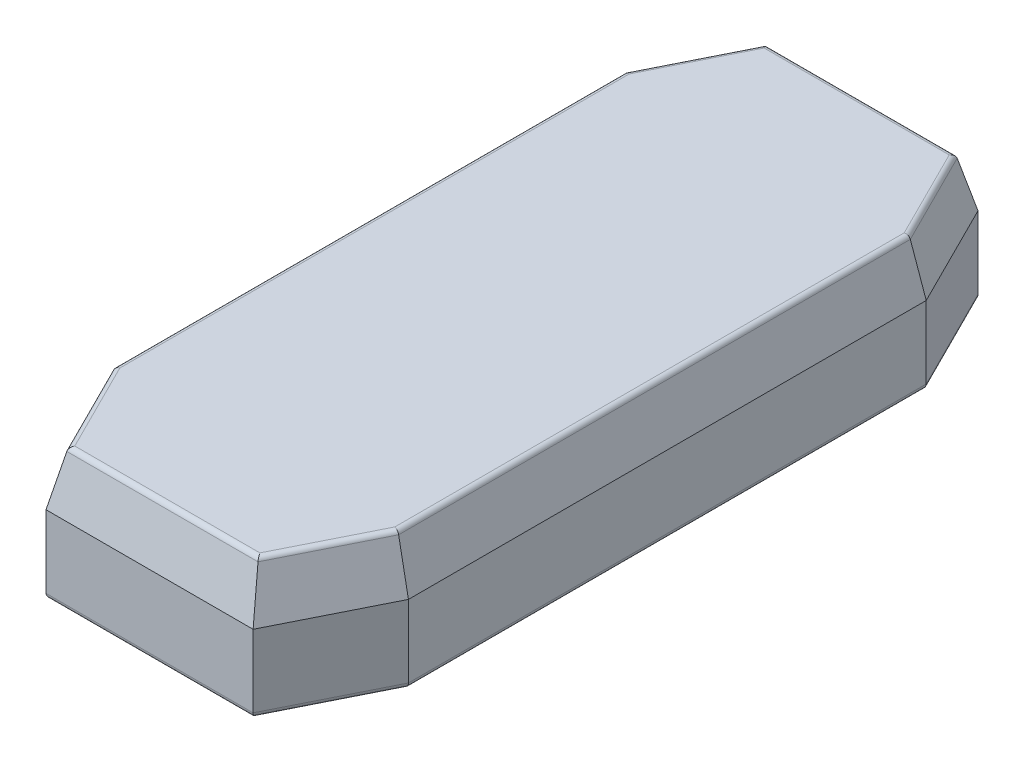
SolidWorks part; units mm, degrees
ref_plane "Front Plane" through (0, 0, 0) normal (0, 0, 1) x (1, 0, 0)
ref_plane "Top Plane" through (0, 0, 0) normal (0, 1, 0) x (1, 0, 0)
ref_plane "Right Plane" through (0, 0, 0) normal (1, 0, 0) x (0, 0, -1)
sketch "Sketch1" plane through (0, 0, 0) normal (0, 1, 0) x (1, 0, 0)
  line L0 (-7.62, 12.7) -> (-5.08, 17.78)
  line L1 (-5.08, 17.78) -> (5.08, 17.78)
  line L2 (-7.62, 12.7) -> (-7.62, -12.7)
  line L3 (-5.08, -17.78) -> (5.08, -17.78)
  line L4 (7.62, 12.7) -> (7.62, -12.7)
  line L5 (-7.62, 17.78) -> (7.62, -17.78) construction
  line L6 (-7.62, -17.78) -> (7.62, 17.78) construction
  line L7 (5.08, 17.78) -> (7.62, 12.7)
  line L8 (5.08, -17.78) -> (7.62, -12.7)
  line L9 (-7.62, -12.7) -> (-5.08, -17.78)
  point P0 (0, 0)
  dimension "D1" = 15.24
  dimension "D2" = 35.56
  dimension "D3" = 2.54
  dimension "D4" = 5.08
  dimension "D5" = 2.54
  dimension "D6" = 5.08
  dimension "D7" = 2.54
  dimension "D8" = 5.08
  dimension "D9" = 5.08
  dimension "D10" = 2.54
extrude "Boss-Extrude1" add sketch "Sketch1" along normal blind 2.54 draft 15
sketch "Stem" plane through (0, 0, 0) normal (0, -1, 0) x (1, 0, 0)
  line L1 (-0.5625, 2.075) -> (0.5625, 2.075)
  line L2 (-0.5625, 2.075) -> (-0.5625, -2.075)
  line L3 (-0.5625, -2.075) -> (0.5625, -2.075)
  line L4 (0.5625, 2.075) -> (0.5625, -2.075)
  line L5 (-0.5625, 2.075) -> (0.5625, -2.075) construction
  line L6 (-0.5625, -2.075) -> (0.5625, 2.075) construction
  line L7 (2.0625, 0.6625) -> (-2.0625, 0.6625)
  line L8 (2.0625, 0.6625) -> (2.0625, -0.6625)
  line L9 (2.0625, -0.6625) -> (-2.0625, -0.6625)
  line L10 (-2.0625, 0.6625) -> (-2.0625, -0.6625)
  line L11 (2.0625, 0.6625) -> (-2.0625, -0.6625) construction
  line L12 (2.0625, -0.6625) -> (-2.0625, 0.6625) construction
  line L13 (-2.5, 2.375) -> (2.5, 2.375)
  line L14 (-3, 1.875) -> (-3, -1.875)
  line L15 (-2.5, -2.375) -> (2.5, -2.375)
  line L16 (3, 1.875) -> (3, -1.875)
  line L17 (-3, 2.375) -> (3, -2.375) construction
  line L18 (-3, -2.375) -> (3, 2.375) construction
  arc A0 (-3, -1.875) -> (-2.5, -2.375) centre (-2.5, -1.875) ccw
  arc A1 (-2.5, 2.375) -> (-3, 1.875) centre (-2.5, 1.875) ccw
  arc A2 (2.5, -2.375) -> (3, -1.875) centre (2.5, -1.875) ccw
  arc A3 (2.5, 2.375) -> (3, 1.875) centre (2.5, 1.875) cw
  point P0 (0, 0)
  point P6 (0, 0)
  point P11 (0, 0)
  dimension "D7" = 0.5
  dimension "D1" = 4.15
  dimension "D2" = 1.125
  dimension "D3" = 1.325
  dimension "D4" = 4.125
  dimension "D5" = 4.75
  dimension "D6" = 6
extrude "Boss-Extrude2" add sketch "Stem" along normal blind 3.8 contours A3 L13 A1 L14 A0 L15 A2 L16 L10 L7 L2 L1 L4 L8 L9 L3 region at (0, 0, 2.2985)
fillet "Fillet2" radius 0.1 8 edges at (-2.8536, -3.8, -2.2286) (-3, -3.8, 0) (-2.8536, -3.8, 2.2286) (0, -3.8, 2.375) (2.8536, -3.8, 2.2286) (3, -3.8, 0) (2.8536, -3.8, -2.2286) (0, -3.8, -2.375)
chamfer "Chamfer1" distance 0.2 angle 45 11 edges at (-0.5625, -3.8, -1.3688) (-1.3125, -3.8, -0.6625) (-2.0625, -3.8, 0) (0.5625, -3.8, -1.3688) (1.3125, -3.8, -0.6625) (2.0625, -3.8, 0) (1.3125, -3.8, 0.6625) (0.5625, -3.8, 1.3687) (0, -3.8, 2.075) (-0.5625, -3.8, 1.3687) (-1.3125, -3.8, 0.6625)
sketch "Sketch3" plane through (0, 0, 0) normal (0, -1, 0) x (1, 0, 0)
  line L0 (-7.62, 12.7) -> (-7.62, -12.7)
  line L1 (-7.62, -12.7) -> (-5.08, -17.78)
  line L2 (-5.08, -17.78) -> (5.08, -17.78)
  line L3 (5.08, -17.78) -> (7.62, -12.7)
  line L4 (7.62, -12.7) -> (7.62, 12.7)
  line L5 (7.62, 12.7) -> (5.08, 17.78)
  line L6 (5.08, 17.78) -> (-5.08, 17.78)
  line L7 (-5.08, 17.78) -> (-7.62, 12.7)
  line L44 (-6.35, -12.4002) -> (-4.2951, -16.51)
  line L45 (-4.2951, -16.51) -> (4.2951, -16.51)
  line L46 (4.2951, -16.51) -> (6.35, -12.4002)
  line L47 (6.35, -12.4002) -> (6.35, 12.4002)
  line L48 (6.35, 12.4002) -> (4.2951, 16.51)
  line L49 (4.2951, 16.51) -> (-4.2951, 16.51)
  line L50 (-4.2951, 16.51) -> (-6.35, 12.4002)
  line L51 (-6.35, 12.4002) -> (-6.35, -12.4002)
  line L52 (-6.35, -12.4002) -> (-4.2951, -16.51)
  line L53 (-4.2951, -16.51) -> (4.2951, -16.51)
  line L54 (4.2951, -16.51) -> (6.35, -12.4002)
  line L55 (6.35, -12.4002) -> (6.35, 12.4002)
  line L56 (6.35, 12.4002) -> (4.2951, 16.51)
  line L57 (4.2951, 16.51) -> (-4.2951, 16.51)
  line L58 (-4.2951, 16.51) -> (-6.35, 12.4002)
  line L59 (-6.35, 12.4002) -> (-6.35, -12.4002)
  dimension "D1" = 1.27
extrude "Boss-Extrude3" add sketch "Sketch3" along normal blind 3.8
fillet "Fillet3" radius 0.25 16 edges at (0, -3.8, -16.51) (5.3225, -3.8, -14.4551) (6.35, -3.8, 0) (5.3225, -3.8, 14.4551) (0, -3.8, 16.51) (-5.3225, -3.8, 14.4551) (-6.35, -3.8, 0) (-5.3225, -3.8, -14.4551) (0, -3.8, 17.78) (6.35, -3.8, 15.24) (7.62, -3.8, 0) (6.35, -3.8, -15.24) (0, -3.8, -17.78) (-6.35, -3.8, -15.24) (-7.62, -3.8, 0) (-6.35, -3.8, 15.24)
fillet "Fillet5" radius 0.5 16 edges at (0, 0, 2.375) (-2.8536, 0, 2.2286) (-3, 0, 0) (-2.8536, 0, -2.2286) (0, 0, -2.375) (2.8536, 0, -2.2286) (3, 0, 0) (2.8536, 0, 2.2286) (-5.3225, 0, 14.4551) (0, 0, 16.51) (5.3225, 0, 14.4551) (6.35, 0, 0) (5.3225, 0, -14.4551) (0, 0, -16.51) (-5.3225, 0, -14.4551) (-6.35, 0, 0)
fillet "Fillet6" radius 0.1 12 edges at (-1.3125, 0, 0.6625) (-0.5625, 0, 1.3687) (0, 0, 2.075) (0.5625, 0, 1.3687) (1.3125, 0, 0.6625) (2.0625, 0, 0) (1.3125, 0, -0.6625) (0.5625, 0, -1.3688) (0, 0, -2.075) (-0.5625, 0, -1.3688) (-1.3125, 0, -0.6625) (-2.0625, 0, 0)
fillet "Fillet7" radius 0.25 8 edges at (5.7994, 2.54, -14.8194) (6.9394, 2.54, 0) (5.7994, 2.54, 14.8194) (0, 2.54, 17.0994) (-5.7994, 2.54, 14.8194) (-6.9394, 2.54, 0) (-5.7994, 2.54, -14.8194) (0, 2.54, -17.0994)
